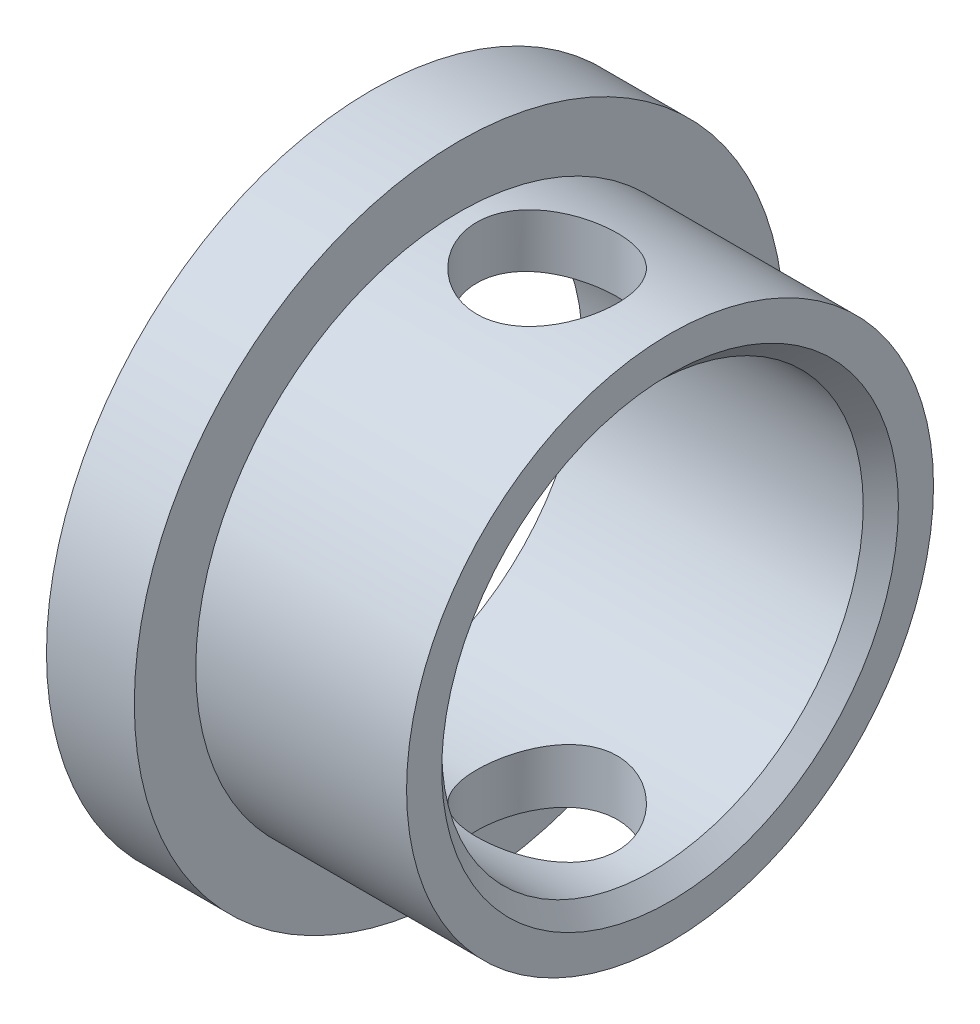
SolidWorks part; units mm, degrees
material "ABS"
ref_plane "Płaszczyzna przednia" through (0, 0, 0) normal (0, 0, 1) x (1, 0, 0)
ref_plane "Płaszczyzna górna" through (0, 0, 0) normal (0, 1, 0) x (1, 0, 0)
ref_plane "Płaszczyzna prawa" through (0, 0, 0) normal (1, 0, 0) x (0, 0, -1)
sketch "Szkic1" plane through (0, 0, 0) normal (1, 0, 0) x (0, 0, -1)
  circle A0 centre (0, 0) radius 12
  circle A1 centre (0, 0) radius 15
  dimension "D1" = 24
  dimension "D2" = 30
extrude "Dodanie-wyciągnięcie1" add sketch "Szkic1" along normal blind 12
sketch "Szkic2" plane through (0, 0, 0) normal (-1, 0, 0) x (0, 0, 1)
  circle A0 centre (0, 0) radius 12 construction
  circle A1 centre (0, 0) radius 12
  circle A2 centre (0, 0) radius 18.5
  dimension "D1" = 37
extrude "Dodanie-wyciągnięcie2" add sketch "Szkic2" along normal blind 5
chamfer "Sfazowanie1" distance 1 angle 45 1 edges at (12, 0, -12)
sketch "Szkic3" plane through (0, 0, 0) normal (0, 1, 0) x (1, 0, 0)
  line L0 (-5, 18.5) -> (-5, -18.5) construction
  circle A0 centre (5, 0) radius 4
  dimension "D1" = 8
  dimension "D2" = 10
extrude "Wytnij-wyciągnięcie1" cut sketch "Szkic3" against normal through all and the other way through all
